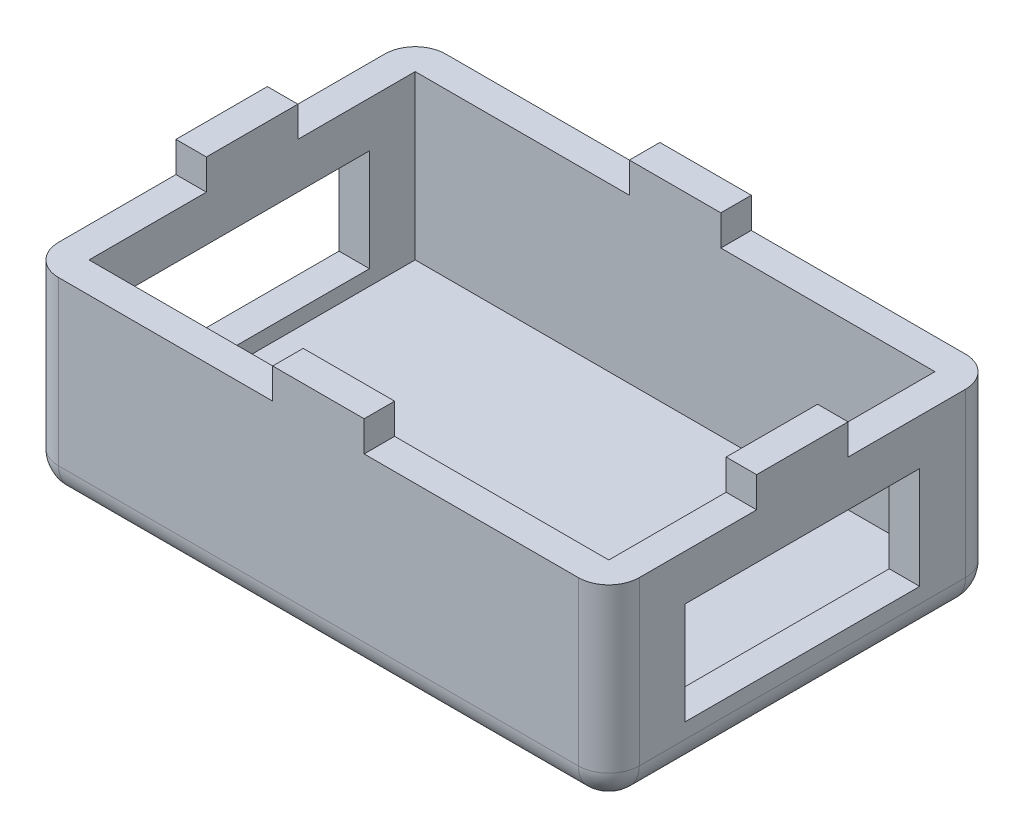
SolidWorks part; units mm, degrees
ref_plane "Front Plane" through (0, 0, 0) normal (0, 0, 1) x (1, 0, 0)
ref_plane "Top Plane" through (0, 0, 0) normal (0, 1, 0) x (1, 0, 0)
ref_plane "Right Plane" through (0, 0, 0) normal (1, 0, 0) x (0, 0, -1)
sketch "Sketch1" plane through (0, 0, 0) normal (0, 1, 0) x (1, 0, 0)
  line L1 (-19.05, 12.7) -> (19.05, 12.7)
  line L2 (-19.05, 12.7) -> (-19.05, -12.7)
  line L3 (-19.05, -12.7) -> (19.05, -12.7)
  line L4 (19.05, 12.7) -> (19.05, -12.7)
  point P0 (0, 0)
  dimension "D1" = 25.4
  dimension "D2" = 38.1
  dimension "D3" = 12.7
  dimension "D4" = 19.05
extrude "Boss-Extrude1" add sketch "Sketch1" along normal blind 12.7
sketch "Sketch2" plane through (0, 12.7, 0) normal (0, 1, 0) x (1, 0, 0)
  line L0 (19.05, 12.7) -> (-19.05, 12.7) construction
  line L1 (-17.05, 10.7) -> (17.05, 10.7)
  line L2 (-17.05, 10.7) -> (-17.05, -10.7)
  line L3 (-17.05, -10.7) -> (17.05, -10.7)
  line L4 (17.05, 10.7) -> (17.05, -10.7)
  line L5 (19.05, -12.7) -> (19.05, 12.7) construction
  line L6 (-19.05, -12.7) -> (19.05, -12.7) construction
  line L7 (-19.05, 12.7) -> (-19.05, -12.7) construction
  point P0 (0, 0)
  dimension "D1" = 2
  dimension "D2" = 2
  dimension "D3" = 2
  dimension "D4" = 2
extrude "Cut-Extrude1" cut sketch "Sketch2" against normal blind 10.7
sketch "Sketch3" plane through (-19.05, 0, 0) normal (-1, 0, 0) x (0, 0, 1)
  line L1 (-7.7, 9.7) -> (7.7, 9.7)
  line L2 (-7.7, 9.7) -> (-7.7, 3)
  line L3 (-7.7, 3) -> (7.7, 3)
  line L4 (7.7, 9.7) -> (7.7, 3)
  line L5 (-12.7, 12.7) -> (-12.7, 0) construction
  line L11 (12.7, 12.7) -> (12.7, 0) construction
  line L13 (-12.7, 12.7) -> (12.7, 12.7) construction
  line L14 (-12.7, 0) -> (12.7, 0) construction
  point P0 (0, 6.2)
  dimension "D1" = 12.7
  dimension "D2" = 3
  dimension "D3" = 3
  dimension "D4" = 12.7
  dimension "D5" = 6.7
  dimension "D6" = 5
  dimension "D7" = 5
extrude "Cut-Extrude2" cut sketch "Sketch3" against normal through all
sketch "Sketch4" plane through (19.05, 0, 0) normal (1, 0, 0) x (0, 0, -1)
  line L2 (-2.9999, 14.7) -> (2.9999, 14.7)
  line L5 (-2.9999, 14.7) -> (-2.9999, 12.7)
  line L6 (-12.7, 12.7) -> (12.7, 12.7) construction
  line L7 (-2.9999, 12.7) -> (2.9999, 12.7)
  line L8 (2.9999, 12.7) -> (2.9999, 14.7)
  point P5 (0, 12.7)
  point P8 (0, 14.7)
  dimension "D1" = 2
  dimension "D3" = 5.9998
extrude "Boss-Extrude2" add sketch "Sketch4" against normal blind 2
mirror "Mirror1" about plane through (0, 0, 0) normal (1, 0, 0) of "Boss-Extrude2"
sketch "Sketch5" plane through (0, 0, -12.7) normal (0, 0, -1) x (-1, 0, 0)
  line L2 (-2.9996, 14.7) -> (2.9996, 14.7)
  line L4 (-2.9996, 14.7) -> (-2.9996, 12.7)
  line L5 (-19.05, 12.7) -> (19.05, 12.7) construction
  line L6 (-2.9996, 12.7) -> (2.9996, 12.7)
  line L7 (2.9996, 12.7) -> (2.9996, 14.7)
  point P5 (0, 12.7)
  point P8 (0, 14.7)
  dimension "D1" = 2
  dimension "D3" = 5.9991
extrude "Boss-Extrude3" add sketch "Sketch5" against normal blind 2
mirror "Mirror2" about plane through (0, 0, 0) normal (0, 0, 1) of "Boss-Extrude3"
sketch "Sketch6" plane through (0, 0, 0) normal (0, -1, 0) x (-1, 0, 0)
  line L0 (-19.05, 4.7) -> (19.05, 4.7) construction
  line L4 (-19.05, -12.7) -> (-19.05, 12.7) construction
  line L5 (19.05, 12.7) -> (19.05, -12.7) construction
  line L6 (-19.05, 12.7) -> (19.05, 12.7) construction
  text T0 "<b>Inertial</b>\r\n<b>Measurement</b>\r\n<b>Unit</b>" font "Courier New" height in points 11
  dimension "D1" = 8
extrude "Cut-Extrude3" cut sketch "Sketch6" against normal blind 1
fillet "Fillet1" radius 2 8 edges at (19.05, 0, 0) (0, 0, 12.7) (0, 0, -12.7) (-19.05, 0, 0) (-19.05, 6.35, -12.7) (-19.05, 6.35, 12.7) (19.05, 6.35, 12.7) (19.05, 6.35, -12.7)
